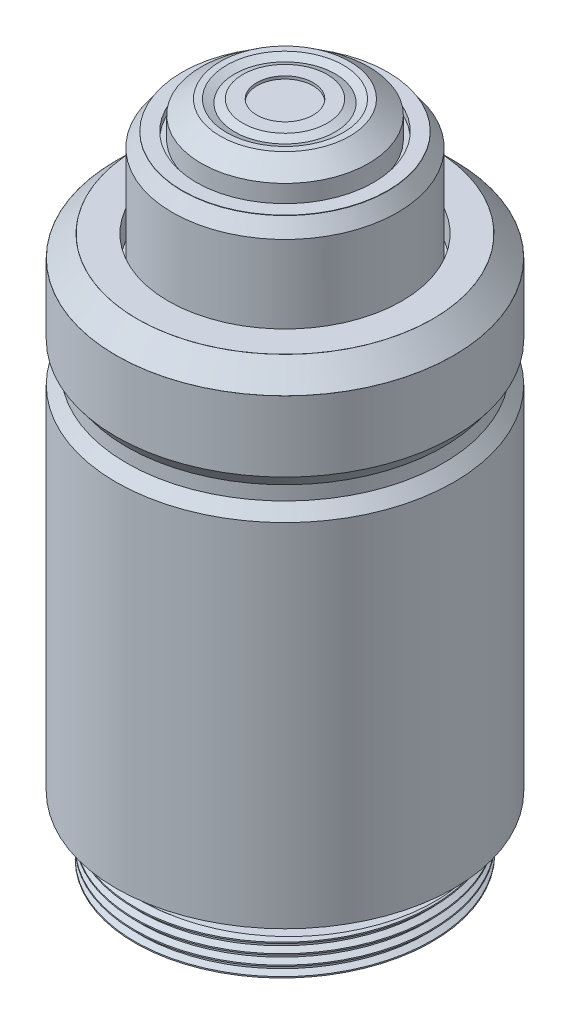
SolidWorks part; units mm, degrees
ref_plane "Alzado" through (0, 0, 0) normal (0, 0, 1) x (1, 0, 0)
ref_plane "Planta" through (0, 0, 0) normal (0, 1, 0) x (1, 0, 0)
ref_plane "Vista lateral" through (0, 0, 0) normal (1, 0, 0) x (0, 0, -1)
sketch "Croquis1" plane through (0, 0, 0) normal (0, 1, 0) x (1, 0, 0)
  circle A0 centre (0, 0) radius 12
  dimension "D1" = 24
extrude "Saliente-Extruir1" add sketch "Croquis1" along normal blind 25
sketch "Croquis3" plane through (0, 25, 0) normal (0, 1, 0) x (1, 0, 0)
  circle A0 centre (0, 0) radius 11.25
  dimension "D1" = 22.5
extrude "Saliente-Extruir2" add sketch "Croquis3" along normal blind 2.8
sketch "Croquis4" plane through (0, 0, 0) normal (0, 0, 1) x (1, 0, 0)
  line L1 (11.25, 25) -> (-11.25, 25) construction
  line L2 (12, 25) -> (-12, 25) construction
  line L3 (-11.25, 25.8) -> (-12, 25)
  line L4 (-12, 25) -> (-11.25, 25)
  line L5 (-11.25, 25.8) -> (0, 25.8)
  line L6 (0, 25.8) -> (0, 25)
  line L7 (0, 25) -> (-11.25, 25)
  dimension "D1" = 0.8
  dimension "D2" = 1.0966
revolve "Revolución1" add sketch "Croquis4" angle 360 about L6
sketch "Croquis5" plane through (0, 27.8, 0) normal (0, 1, 0) x (1, 0, 0)
  circle A0 centre (0, 0) radius 12
extrude "Saliente-Extruir3" add sketch "Croquis5" along normal blind 5
sketch "Croquis6" plane through (0, 0, 0) normal (1, 0, 0) x (0, 0, -1)
  line L1 (-11.25, 27.8) -> (-11.25, 25.8) construction
  line L2 (-11.25, 26.8) -> (-12, 27.8)
  line L3 (-12, 27.8) -> (-11.25, 27.8)
  line L4 (-11.25, 27.8) -> (0, 27.8)
  line L5 (-11.25, 27.8) -> (11.25, 27.8) construction
  line L6 (0, 27.8) -> (0, 26.8)
  line L7 (0, 26.8) -> (-11.25, 26.8)
  dimension "D1" = 1
revolve "Revolución2" add sketch "Croquis6" angle 360 about L6
sketch "Croquis7" plane through (0, 32.8, 0) normal (0, 1, 0) x (1, 0, 0)
  circle A0 centre (0, 0) radius 10.5
  dimension "D1" = 21
extrude "Saliente-Extruir4" add sketch "Croquis7" along normal blind 1.5
sketch "Croquis8" plane through (0, 0, 0) normal (1, 0, 0) x (0, 0, -1)
  line L0 (-11.9938, 32.8) -> (-10.4938, 34.3)
  line L1 (12, 32.8) -> (-12, 32.8) construction
  line L2 (10.5, 34.3) -> (-10.5, 34.3) construction
  line L3 (-10.4938, 34.3) -> (0, 34.3)
  line L4 (0, 34.3) -> (0, 32.8)
  line L5 (0, 32.8) -> (-11.9938, 32.8)
revolve "Revolución3" add sketch "Croquis8" angle 360 about L4
sketch "Croquis9" plane through (0, 34.3, 0) normal (0, 1, 0) x (1, 0, 0)
  circle A0 centre (0, 0) radius 8.3
  dimension "D1" = 16.6
extrude "Cortar-Extruir1" cut sketch "Croquis9" against normal blind 2
sketch "Croquis10" plane through (0, 32.3, 0) normal (0, 1, 0) x (1, 0, 0)
  circle A0 centre (0, 0) radius 8
  dimension "D1" = 16
extrude "Saliente-Extruir5" add sketch "Croquis10" along normal blind 7.3
sketch "Croquis11" plane through (0, 39.6, 0) normal (0, 1, 0) x (1, 0, 0)
  circle A0 centre (0, 0) radius 7.3
  dimension "D1" = 14.6
extrude "Saliente-Extruir6" add sketch "Croquis11" along normal blind 1
sketch "Croquis12" plane through (0, 0, 0) normal (1, 0, 0) x (0, 0, -1)
  line L0 (-7.2805, 40.6) -> (-8, 39.6)
  line L1 (7.3, 40.6) -> (-7.3, 40.6) construction
  line L2 (8, 39.6) -> (-8, 39.6) construction
  line L3 (-8, 39.6) -> (0, 39.6)
  line L4 (0, 39.6) -> (0, 40.6)
  line L5 (0, 40.6) -> (-7.2805, 40.6)
revolve "Revolución4" add sketch "Croquis12" angle 360 about L4
sketch "Croquis13" plane through (0, 40.6, 0) normal (0, 1, 0) x (1, 0, 0)
  circle A0 centre (0, 0) radius 6.3
  dimension "D1" = 12.6
extrude "Cortar-Extruir2" cut sketch "Croquis13" against normal blind 0.5
sketch "Croquis14" plane through (0, 40.1, 0) normal (0, 1, 0) x (1, 0, 0)
  circle A0 centre (0, 0) radius 5.95
  dimension "D1" = 11.9
extrude "Saliente-Extruir7" add sketch "Croquis14" along normal blind 1.5
sketch "Croquis15" plane through (0, 41.6, 0) normal (0, 1, 0) x (1, 0, 0)
  circle A0 centre (0, 0) radius 4.6
  dimension "D1" = 9.2
extrude "Saliente-Extruir8" add sketch "Croquis15" along normal blind 1
sketch "Croquis16" plane through (0, 0, 0) normal (1, 0, 0) x (0, 0, -1)
  line L0 (-5.95, 41.6) -> (-4.6, 42.6)
  line L1 (5.95, 41.6) -> (-5.95, 41.6) construction
  line L2 (4.6, 42.6) -> (-4.6, 42.6) construction
  line L3 (-4.6, 42.6) -> (0, 42.6)
  line L4 (0, 42.6) -> (0, 41.6)
  line L5 (0, 41.6) -> (-5.95, 41.6)
revolve "Revolución5" add sketch "Croquis16" angle 360 about L4
sketch "Croquis17" plane through (0, 42.6, 0) normal (0, 1, 0) x (1, 0, 0)
  circle A0 centre (0, 0) radius 4.15
  dimension "D1" = 8.3
extrude "Cortar-Extruir3" cut sketch "Croquis17" against normal blind 0.25
sketch "Croquis21" plane through (0, 0, 0) normal (0, 0, 1) x (1, 0, 0)
  line L0 (0, 42.35) -> (3.575, 42.35)
  line L1 (4.15, 42.35) -> (-4.15, 42.35) construction
  line L2 (3.575, 42.35) -> (4.15, 42.6)
  line L3 (4.6, 42.6) -> (-4.6, 42.6) construction
  line L4 (4.15, 42.6) -> (-4.15, 42.6) construction
  line L5 (4.15, 42.6) -> (4.15, 41.7665)
  line L6 (4.15, 41.7665) -> (0, 41.7665)
  line L7 (0, 41.7665) -> (0, 42.35)
  dimension "D1" = 3.575
revolve "Revolución8" add sketch "Croquis21" angle 360 about L7
sketch "Croquis22" plane through (0, 42.35, 0) normal (0, 1, 0) x (1, 0, 0)
  circle A0 centre (0, 0) radius 3
  dimension "D1" = 6
extrude "Saliente-Extruir10" add sketch "Croquis22" along normal blind 0.25
sketch "Croquis23" plane through (0, 0, 0) normal (0, 0, 1) x (1, 0, 0)
  line L0 (3, 42.6) -> (3.575, 42.35)
  line L1 (3, 42.6) -> (-3, 42.6) construction
  line L2 (3.575, 42.35) -> (-3.575, 42.35) construction
  line L3 (3.575, 42.35) -> (0, 42.35)
  line L4 (3, 42.35) -> (-3, 42.35) construction
  line L5 (0, 42.35) -> (0, 42.6)
  line L6 (0, 42.6) -> (3, 42.6)
revolve "Revolución9" add sketch "Croquis23" angle 360 about L5
sketch "Croquis24" plane through (0, 0, 0) normal (0, -1, 0) x (1, 0, 0)
  circle A0 centre (0, 0) radius 10.65
  dimension "D1" = 21.3
extrude "Saliente-Extruir11" add sketch "Croquis24" along normal blind 0.5
sketch "Croquis25" plane through (0, 0, 0) normal (1, 0, 0) x (0, 0, -1)
  line L0 (12, 0) -> (10.65, -0.5)
  line L1 (-12, 0) -> (12, 0) construction
  line L2 (-10.65, -0.5) -> (10.65, -0.5) construction
  line L3 (10.65, -0.5) -> (0, -0.5)
  line L4 (0, -0.5) -> (0, 0)
  line L5 (0, 0) -> (12, 0)
revolve "Revolución10" add sketch "Croquis25" angle 360 about L4
sketch "Croquis26" plane through (0, -0.5, 0) normal (0, -1, 0) x (1, 0, 0)
  circle A0 centre (0, 0) radius 9.5
  dimension "D1" = 19
extrude "Saliente-Extruir12" add sketch "Croquis26" along normal blind 1.2
sketch "Croquis27" plane through (0, -1.7, 0) normal (0, -1, 0) x (1, 0, 0)
  circle A0 centre (0, 0) radius 10.16
  dimension "D1" = 20.32
extrude "Saliente-Extruir13" add sketch "Croquis27" along normal blind 2.6
sketch "Croquis28" plane through (0, -4.3, 0) normal (0, -1, 0) x (1, 0, 0)
  circle A0 centre (0, 0) radius 9.45
  circle A1 centre (0, 0) radius 7.5
  dimension "D1" = 18.9
  dimension "D2" = 15
extrude "Saliente-Extruir14" add sketch "Croquis28" along normal blind 0.2
sketch "Croquis29" plane through (0, -4.3, 0) normal (0, -1, 0) x (1, 0, 0)
  circle A0 centre (0, 0) radius 3.75
  dimension "D1" = 7.5
extrude "Cortar-Extruir4" cut sketch "Croquis29" against normal up to surface (36.6 mm away) up to face at (0, 32.3, 8)
sketch "Croquis30" plane through (0, 42.6, 0) normal (0, 1, 0) x (1, 0, 0)
  circle A0 centre (0, 0) radius 2
  dimension "D1" = 4
extrude "Cortar-Extruir5" cut sketch "Croquis30" against normal blind 40.2
sketch "Croquis31" plane through (0, -4.3, 0) normal (0, -1, 0) x (1, 0, 0)
  circle A0 centre (0, 0) radius 3.7484
extrude "Saliente-Extruir15" add sketch "Croquis31" against normal blind 2 separate body
sketch "Croquis32" plane through (0, 42.6, 0) normal (0, 1, 0) x (1, 0, 0)
  circle A0 centre (0, 0) radius 2
extrude "Saliente-Extruir20" add sketch "Croquis32" along normal blind 0.5 separate body
sketch "Croquis33" plane through (0, 43.1, 0) normal (0, 1, 0) x (1, 0, 0)
  circle A0 centre (0, 0) radius 2.0021
extrude "Saliente-Extruir21" add sketch "Croquis33" against normal blind 2.7
sketch "Croquis34" plane through (0, 43.1, 0) normal (0, 1, 0) x (1, 0, 0)
  circle A0 centre (0, 0) radius 2.0021
extrude "Cortar-Extruir7" cut sketch "Croquis34" against normal blind 0.7
thread "Rosca2" pitch 0.7056 start angle 0, offset 0.6, length 12.6, pitch 0.7056, diameter 20.32
ref_plane "Plano3" through (10.16, -4.9, 0) normal (0, 0, 1) x (1, 0, 0)
sketch "Perfil de rosca3" plane through (10.16, -4.9, 0) normal (0, 0, 1) x (1, 0, 0)
  line L0 (0, 0) -> (0, 0.7056) construction
  line L1 (0, 0) -> (0.3819, 0.2205)
  line L2 (0.3819, 0.2205) -> (0.3819, 0.3087)
  line L3 (0.3819, 0.3087) -> (0, 0.5292)
  line L4 (0.3819, 0.2646) -> (0, 0.2646) construction
  line L11 (0, 0) -> (0, 0.5292)
  point P2 (0, 0)
  dimension "Pitch" = 0.7056
  dimension "Profile_Angle" = 60
  dimension "Profile_Land" = 0.0882
  dimension "Profile_Height" = 0.3819
